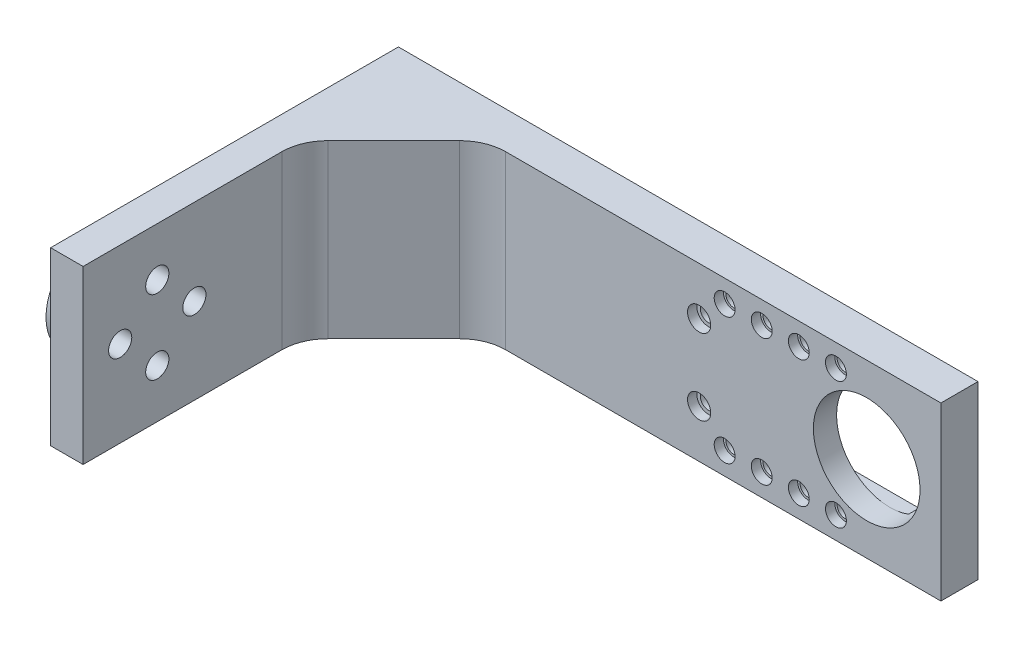
SolidWorks part; units mm, degrees
ref_plane "Front Plane" through (0, 0, 0) normal (0, 0, 1) x (1, 0, 0)
ref_plane "Top Plane" through (0, 0, 0) normal (0, 1, 0) x (1, 0, 0)
ref_plane "Right Plane" through (0, 0, 0) normal (1, 0, 0) x (0, 0, -1)
sketch "Sketch1" plane through (0, 0, 0) normal (0, 1, 0) x (1, 0, 0)
  line L0 (0, 0) -> (0, 75)
  line L1 (0, 75) -> (125, 75)
  line L2 (125, 75) -> (125, 67)
  line L3 (125, 67) -> (7, 67)
  line L4 (7, 67) -> (7, 0)
  line L5 (7, 0) -> (0, 0)
  dimension "D1" = 118
  dimension "D2" = 125
  dimension "D3" = 8
  dimension "D4" = 67
  dimension "D5" = 75
extrude "Boss-Extrude1" add sketch "Sketch1" along normal blind 37
sketch "Sketch2" plane through (0, 0, -75) normal (0, 0, -1) x (-1, 0, 0)
  line L0 (-125, 18.5) -> (-109, 18.5)
  line L1 (-125, 37) -> (-125, 0) construction
  circle A0 centre (-109, 18.5) radius 11.5
  dimension "D2" = 23
  dimension "D1" = 16
extrude "Cut-Extrude1" cut sketch "Sketch2" against normal up to next contours A0 region at (109, 7.3253, -75)
sketch "Sketch3" plane through (0, 0, -75) normal (0, 0, -1) x (-1, 0, 0)
  line L0 (-125, 32.19) -> (-102.36, 32.19)
  line L1 (-125, 37) -> (-125, 0) construction
  line L2 (-102.36, 32.19) -> (-102.36, 37)
  line L3 (-125, 37) -> (0, 37) construction
  line L4 (-125, 18.5) -> (-57.038, 18.5)
  circle A0 centre (-102.36, 32.19) radius 1.75
  circle A1 centre (-94.36, 32.19) radius 1.75
  circle A2 centre (-86.36, 32.19) radius 1.75
  circle A3 centre (-78.36, 32.19) radius 1.75
  circle A4 centre (-78.36, 4.81) radius 1.75
  circle A5 centre (-86.36, 4.81) radius 1.75
  circle A6 centre (-94.36, 4.81) radius 1.75
  circle A7 centre (-102.36, 4.81) radius 1.75
  dimension "D3" = 3.5
  dimension "D1" = 22.64
  dimension "D2" = 4.81
  dimension "D4" = 4
extrude "Cut-Extrude2" cut sketch "Sketch3" against normal up to next contours A5 | A7 | A6 | A4 | A3 | A2 | A1 | A0 region at (86.36, 4.81, -75)
sketch "Sketch4" plane through (0, 0, -75) normal (0, 0, -1) x (-1, 0, 0)
  line L0 (-113, 30) -> (-113, 7)
  line L4 (-113, 30) -> (-75, 30)
  line L5 (-75, 30) -> (-75, 7)
  line L6 (-75, 7) -> (-113, 7)
  dimension "D3" = 23
  dimension "D4" = 38
  dimension "D5" = 38
sketch "Sketch5" plane through (0, 0, 0) normal (-1, 0, 0) x (0, 0, 1)
  circle A1 centre (-16, 10.5) radius 1.75
  circle A2 centre (-24, 18.5) radius 1.75
  circle A3 centre (-16, 26.5) radius 1.75
  circle A4 centre (-8, 18.5) radius 1.75
  point P13 (-16, 18.5)
  dimension "D4" = 3.5
  dimension "D1" = 4
extrude "Cut-Extrude5" cut sketch "Sketch5" against normal up to next
sketch "Sketch6" plane through (0, 0, 0) normal (-1, 0, 0) x (0, 0, 1)
  line L0 (0, 18.5) -> (-16, 18.5)
  line L1 (0, 37) -> (0, 0) construction
  circle A0 centre (-16, 18.5) radius 11
  circle A1 centre (-16, 10.5) radius 1.75 construction
  circle A2 centre (-24, 18.5) radius 1.75 construction
  circle A3 centre (-16, 26.5) radius 1.75 construction
  circle A4 centre (-8, 18.5) radius 1.75 construction
  circle A5 centre (-16, 10.5) radius 1.75
  circle A6 centre (-24, 18.5) radius 1.75
  circle A7 centre (-16, 26.5) radius 1.75
  circle A8 centre (-8, 18.5) radius 1.75
  circle M1 centre (-8, 18.5) radius 1.75
  circle M2 centre (-16, 26.5) radius 1.75
  circle M3 centre (-24, 18.5) radius 1.75
  circle M4 centre (-16, 10.5) radius 1.75
  dimension "D2" = 22
  dimension "D1" = 16
extrude "Boss-Extrude3" add sketch "Sketch6" along normal blind 6 contours A0 M1 M3 M4 M2 region at (0, 18.5, -26.6889)
extrude "Cut-Extrude6" cut sketch "Sketch4" against normal blind 3
sketch "Sketch7" plane through (75, 0, 0) normal (1, 0, 0) x (0, 0, -1)
  line L4 (75, 7) -> (75, 30)
  line L5 (75, 30) -> (72, 30)
  line L6 (72, 30) -> (72, 7)
  line L7 (72, 7) -> (75, 7)
  line L8 (75, 7) -> (75, 30)
  line L9 (75, 30) -> (72, 30)
  line L10 (72, 30) -> (72, 7)
  line L11 (72, 7) -> (75, 7)
  dimension "D1" = 0
extrude "Boss-Extrude4" add sketch "Sketch7" along normal blind 7.5
sketch "Sketch9" plane through (0, 0, -67) normal (0, 0, 1) x (1, 0, 0)
  circle A1 centre (78.36, 32.19) radius 2.25
  circle A2 centre (86.36, 32.19) radius 2.25
  circle A3 centre (94.36, 32.19) radius 2.25
  circle A4 centre (102.36, 32.19) radius 2.25
  circle A6 centre (78.36, 4.81) radius 2.25
  circle A7 centre (86.36, 4.81) radius 2.25
  circle A8 centre (94.36, 4.81) radius 2.25
  circle A9 centre (102.36, 4.81) radius 2.25
  dimension "D2" = 4.5
  dimension "D3" = 4.5
  dimension "D4" = 4.5
  dimension "D5" = 4.5
  dimension "D7" = 4.5
  dimension "D8" = 4.5
  dimension "D9" = 4.5
  dimension "D10" = 4.5
extrude "Cut-Extrude8" cut sketch "Sketch9" against normal blind 2
sketch "Sketch10" plane through (7, 0, 0) normal (1, 0, 0) x (0, 0, -1)
  circle A0 centre (24, 18.5) radius 2.5
  circle A1 centre (16, 10.5) radius 2.5
  circle A2 centre (8, 18.5) radius 2.5
  circle A3 centre (16, 26.5) radius 2.5
  dimension "D1" = 5
  dimension "D2" = 5
  dimension "D3" = 5
  dimension "D4" = 5
extrude "Cut-Extrude9" cut sketch "Sketch10" against normal blind 5
chamfer "Chamfer1" distance 20 angle 45 1 edges at (7, 18.5, -67)
fillet "Fillet5" radius 10 2 edges at (7, 18.5, -47) (27, 18.5, -67)
sketch "Sketch11" plane through (0, 0, -67) normal (0, 0, 1) x (1, 0, 0)
  line L0 (78.36, 4.81) -> (72.86, 4.81)
  line L1 (72.86, 4.81) -> (72.86, 10.31)
  line L2 (31.1421, 18.5) -> (74.9862, 18.5)
  line L3 (31.1421, 37) -> (31.1421, 0) construction
  circle A0 centre (72.86, 10.31) radius 1.75
  circle A1 centre (72.86, 26.69) radius 1.75
  dimension "D3" = 3.5
  dimension "D1" = 5.5
  dimension "D2" = 5.5
extrude "Cut-Extrude10" cut sketch "Sketch11" against normal up to next contours A0 | A1 region at (74.0624, 9.1076, -67) region at (72.86, 26.69, -67)
sketch "Sketch12" plane through (0, 0, -67) normal (0, 0, 1) x (1, 0, 0)
  circle A0 centre (72.86, 10.31) radius 2.5
  circle A1 centre (72.86, 26.69) radius 2.5
  dimension "D1" = 5
  dimension "D2" = 5
extrude "Cut-Extrude11" cut sketch "Sketch12" against normal blind 2
